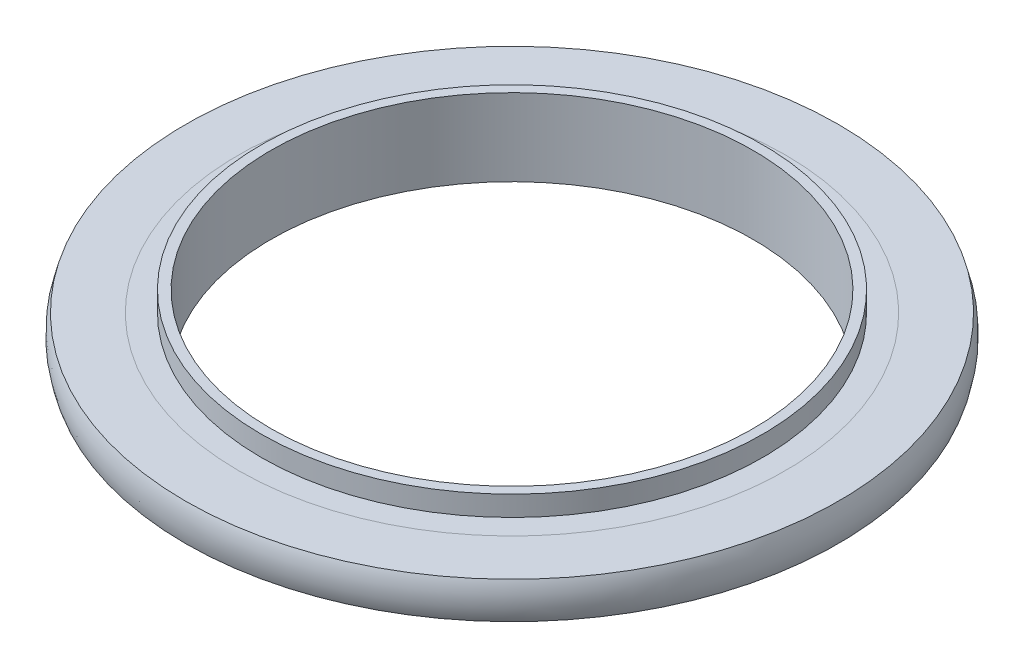
SolidWorks part; units mm, degrees
material "AISI 304"
ref_plane "Front Plane" through (0, 0, 0) normal (0, 0, 1) x (1, 0, 0)
ref_plane "Top Plane" through (0, 0, 0) normal (0, 1, 0) x (1, 0, 0)
ref_plane "Right Plane" through (0, 0, 0) normal (1, 0, 0) x (0, 0, -1)
sketch "Sketch1" plane through (0, 0, 0) normal (0, 0, 1) x (1, 0, 0)
  line L0 (0, 4) -> (0, -4) construction
  line L1 (25, 4) -> (25, -4)
  line L2 (25, -4) -> (26, -4)
  line L3 (26, -4) -> (26, -1.905)
  line L4 (26, -1.905) -> (28.3542, -1.905)
  line L5 (25, 4) -> (26, 4)
  line L6 (26, 4) -> (26, 1.905)
  line L7 (26, 1.905) -> (28.3542, 1.905)
  arc A0 (28.3542, 1.905) -> (28.3542, -1.905) centre (33.3, 0) ccw
  dimension "D5" = 5.3
  dimension "D1" = 8
  dimension "D2" = 3.81
  dimension "InnerD" = 50
  dimension "LipD" = 52
  dimension "SealD" = 56
revolve "Revolve1" add sketch "Sketch1" angle 360 about L0
sketch "Sketch2" plane through (0, 0, 0) normal (0, 0, 1) x (1, 0, 0)
  line L0 (28.3542, 1.905) -> (33.8458, 1.905)
  line L1 (28.3542, -1.905) -> (33.8458, -1.905)
  line L2 (31.1, 1.905) -> (31.1, -1.905) construction
  line L4 (31.1, 0) -> (30.7, 0) construction
  line L5 (0, -4) -> (0, 4) construction
  arc A0 (28.3542, 1.905) -> (28.3542, -1.905) centre (33.3, 0) ccw construction
  arc A1 (28.3542, 1.905) -> (28.3542, -1.905) centre (33.3, 0) ccw
  arc A2 (33.8458, 1.905) -> (33.8458, -1.905) centre (28.9, 0) cw
  circle A3 centre (30.7, 0) radius 2.7 construction
  dimension "D1" = 5.4
  dimension "D2" = 6.2
revolve "Revolve2" add sketch "Sketch2" angle 360 about L5
ref_axis "Axis1" through (0, -4, 0) along (0, 1, 0)
